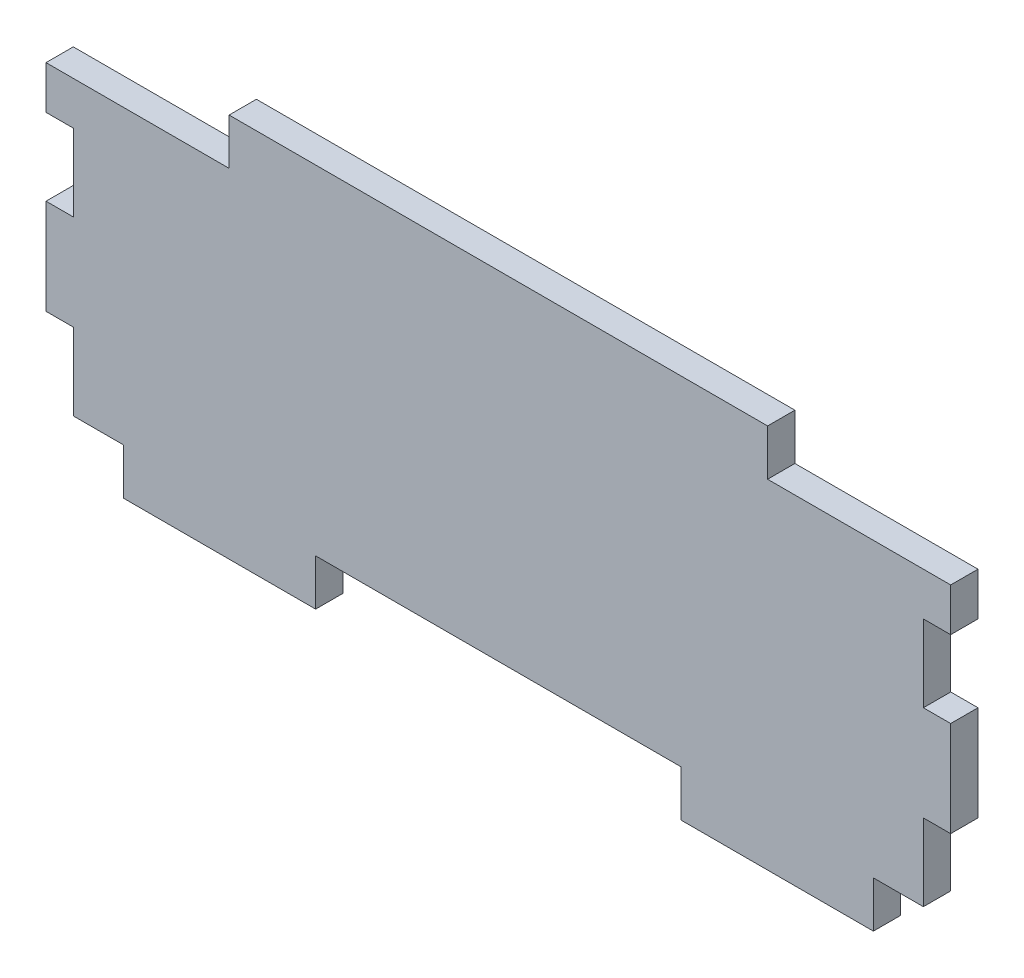
SolidWorks part; units mm, degrees
ref_plane "Front Plane" through (0, 0, 0) normal (0, 0, 1) x (1, 0, 0)
ref_plane "Top Plane" through (0, 0, 0) normal (0, 1, 0) x (1, 0, 0)
ref_plane "Right Plane" through (0, 0, 0) normal (1, 0, 0) x (0, 0, -1)
sketch "Sketch1" plane through (0, 0, 0) normal (0, 0, 1) x (1, 0, 0)
  line L0 (1.8034, 9.8044) -> (0, 9.8044) construction
  line L1 (1.8034, 16.1036) -> (1.8034, 9.8044) construction
  line L2 (1.8034, 16.1036) -> (0, 16.1036) construction
  line L3 (0, 21.1836) -> (0, 16.1036) construction
  line L4 (1.8034, 21.1836) -> (0, 21.1836) construction
  line L5 (1.8034, 24.0284) -> (1.8034, 21.1836) construction
  line L7 (1.8034, 9.8044) -> (0, 9.8044)
  line L8 (1.8034, 16.1036) -> (1.8034, 9.8044)
  line L9 (1.8034, 16.1036) -> (0, 16.1036)
  line L10 (0, 21.1836) -> (0, 16.1036)
  line L11 (1.8034, 21.1836) -> (0, 21.1836)
  line L12 (1.8034, 24.0284) -> (1.8034, 21.1836)
  line L13 (0, 9.8044) -> (0, 4.7244)
  line L14 (1.8034, 24.0284) -> (-10.287, 24.0284)
  line L15 (-10.287, 24.0284) -> (-10.287, 27.0764)
  line L16 (-10.287, 27.0764) -> (-45.847, 27.0764)
  line L17 (-45.847, 27.0764) -> (-45.847, 24.0284)
  line L18 (-45.847, 24.0284) -> (-57.9374, 24.0284)
  line L19 (-28.067, 27.0764) -> (-28.067, 4.7244) construction
  line L20 (-56.134, 9.8044) -> (-56.134, 4.7244)
  line L21 (-57.9374, 24.0284) -> (-57.9374, 21.1836)
  line L22 (-57.9374, 21.1836) -> (-56.134, 21.1836)
  line L23 (-56.134, 21.1836) -> (-56.134, 16.1036)
  line L24 (-57.9374, 16.1036) -> (-56.134, 16.1036)
  line L25 (-57.9374, 16.1036) -> (-57.9374, 9.8044)
  line L26 (-57.9374, 9.8044) -> (-56.134, 9.8044)
  line L27 (0, 4.7244) -> (-3.302, 4.7244)
  line L28 (-3.302, 4.7244) -> (-3.302, 1.6764)
  line L29 (-3.302, 1.6764) -> (-16.002, 1.6764)
  line L30 (-16.002, 1.6764) -> (-16.002, 4.7244)
  line L31 (-16.002, 4.7244) -> (-40.132, 4.7244)
  line L32 (-40.132, 4.7244) -> (-40.132, 1.6764)
  line L33 (-40.132, 1.6764) -> (-52.832, 1.6764)
  line L34 (-52.832, 1.6764) -> (-52.832, 4.7244)
  line L35 (-52.832, 4.7244) -> (-56.134, 4.7244)
  dimension "D1" = 56.134
  dimension "D2" = 35.56
  dimension "D3" = 3.048
  dimension "D4" = 16.002
  dimension "D5" = 16.002
  dimension "D6" = 3.048
  dimension "D7" = 12.7
extrude "Boss-Extrude1" add sketch "Sketch1" along normal blind 1.8034
